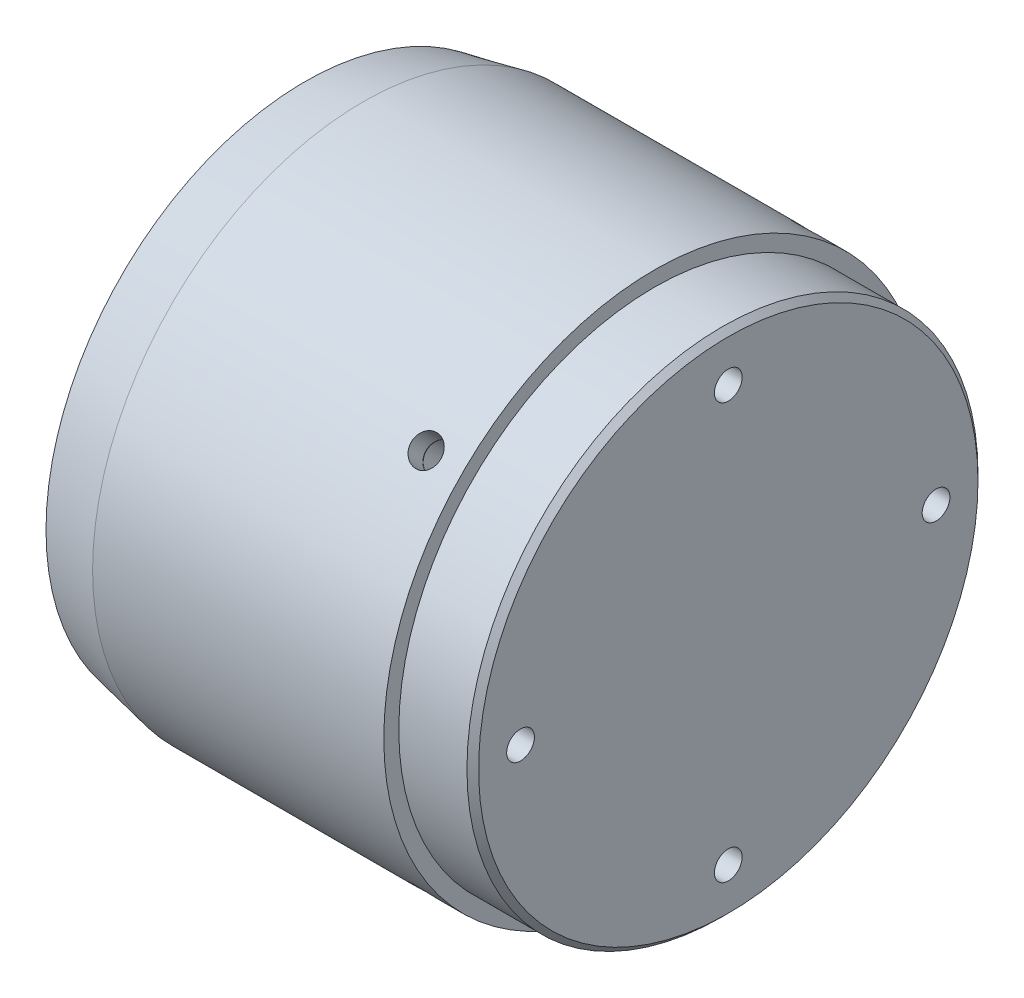
SolidWorks part; units mm, degrees
material "6061 Alloy"
ref_plane "Front Plane" through (0, 0, 0) normal (0, 0, 1) x (1, 0, 0)
ref_plane "Top Plane" through (0, 0, 0) normal (0, 1, 0) x (1, 0, 0)
ref_plane "Right Plane" through (0, 0, 0) normal (1, 0, 0) x (0, 0, -1)
sketch "Sketch1" plane through (0, 0, 0) normal (0, 0, 1) x (1, 0, 0)
  line L0 (0, 0) -> (74.8253, 0) construction
  line L1 (10, 46.45) -> (60, 46.45)
  line L6 (0, 44.45) -> (10, 46.45)
  line L7 (0, 0) -> (0, 44.45) construction
  line L17 (60, 44.45) -> (60, 46.45)
  line L18 (60, 44.45) -> (60, 42.85)
  line L19 (60, 42.85) -> (40, 42.85)
  line L20 (40, 42.85) -> (40, 44.45)
  line L21 (40, 44.45) -> (0, 44.45)
  line L22 (40, 44.45) -> (60, 44.45) construction
  dimension "D1" = 88.9
  dimension "D2" = 60
  dimension "D3" = 10
  dimension "D4" = 20
  dimension "D5" = 2
  dimension "D6" = 1.6
revolve "Revolve1" add sketch "Sketch1" angle 360 about L0
sketch "Sketch2" plane through (0, 0, 0) normal (0, 0, 1) x (1, 0, 0)
  line L0 (0, 0) -> (60, 0) construction
  line L2 (60, -46.45) -> (60, 46.45) construction
  line L3 (60, 42.77) -> (47.3, 42.77)
  line L4 (60, 42.77) -> (60, 28.575)
  line L5 (60, 28.575) -> (47.3, 28.575)
  line L6 (47.3, 42.77) -> (47.3, 28.575)
  line L7 (60, -46.45) -> (60, 46.45) construction
  line L8 (60, 42.85) -> (0, 42.85) construction
  line L9 (0, 44.45) -> (0, -44.45) construction
  dimension "D1" = 12.7
  dimension "D2" = 28.575
  dimension "D3" = 0.08
revolve "Revolve2" add sketch "Sketch2" angle 360 about L0
sketch "Sketch3" plane through (60, 0, 0) normal (1, 0, 0) x (0, 0, -1)
  line L0 (-35.6725, 0) -> (0, 0) construction
  line L1 (0, 35.6725) -> (0, 0) construction
  line L2 (35.6725, 0) -> (0, 0) construction
  line L3 (0, -35.6725) -> (0, 0) construction
  line L4 (-28.575, 0) -> (-42.77, 0) construction
  circle A0 centre (-35.6725, 0) radius 2.3812
  circle A1 centre (0, 35.6725) radius 2.3812
  circle A2 centre (35.6725, 0) radius 2.3812
  circle A3 centre (0, -35.6725) radius 2.3812
  circle A4 centre (0, 0) radius 28.575 construction
  circle A5 centre (0, 0) radius 42.77 construction
  point P13 (0, 0)
  dimension "D1" = 4.7625
  dimension "D3" = 4
extrude "Cut-Extrude1" cut sketch "Sketch3" against normal through all
ref_plane "Plane1" through (0, 32.8451, 32.8451) normal (0, 0.7071, 0.7071) x (-1, 0, 0)
sketch "Sketch4" plane through (0, 32.8451, 32.8451) normal (0, 0.7071, 0.7071) x (-1, 0, 0)
  line L0 (-53.65, 0) -> (0, 0) construction
  line L1 (-60, 46.45) -> (-60, -46.45) construction
  circle A0 centre (-53.65, 0) radius 2.54
  dimension "D1" = 5.08
  dimension "D2" = 6.35
extrude "Cut-Extrude2" cut sketch "Sketch4" against normal up to surface (17.9881 mm away) up to face at (60, 0, 28.575)
ref_axis "Axis1" through (60, 0, 0) along (-1, 0, 0)
pattern_circular "CirPattern1" count 4 over 360 about axis through (60, 0, 0) along (-1, 0, 0) of "Cut-Extrude2"
sketch "Sketch5" plane through (60, 0, 0) normal (1, 0, 0) x (0, 0, -1)
  line L0 (0, 0) -> (-20.2056, 20.2056) construction
  line L3 (0, 0) -> (0, 35.6725) construction
  line L5 (-21.9733, 11.3667) -> (-18.4378, 29.0444) construction
  line L6 (-29.0444, 18.4378) -> (-11.3667, 21.9733) construction
  line L7 (-29.0444, 18.4378) -> (-18.4378, 29.0444)
  line L8 (-18.4378, 29.0444) -> (-11.3667, 21.9733)
  line L9 (-11.3667, 21.9733) -> (-21.9733, 11.3667)
  line L10 (-21.9733, 11.3667) -> (-29.0444, 18.4378)
  circle A0 centre (0, 0) radius 28.575 construction
  point P10 (-20.2056, 20.2056)
  point P12 (-20.2056, 20.2056)
  dimension "D1" = 45
  dimension "D2" = 15
  dimension "D3" = 10
extrude "Cut-Extrude3" cut sketch "Sketch5" against normal up to surface (12.7 mm away) up to face at (47.3, 0, 33.2912)
fillet "Fillet1" radius 3.2 4 edges at (53.65, 14.1939, 24.8005) (53.65, 24.8005, 14.1939) (53.65, 18.4378, 29.0444) (53.65, 29.0444, 18.4378)
fillet "Fillet2" radius 3.2 1 edges at (40, 0, 44.45)
sketch "Sketch6" plane through (60, 0, 0) normal (1, 0, 0) x (0, 0, -1)
  circle A0 centre (0, 0) radius 43.875
  circle A1 centre (-35.6725, 0) radius 2.3813 construction
  circle A2 centre (0, -35.6725) radius 2.3812 construction
  circle A3 centre (35.6725, 0) radius 2.3813 construction
  circle A4 centre (0, 35.6725) radius 2.3812 construction
  circle A5 centre (-35.6725, 0) radius 2.3812
  circle A6 centre (0, -35.6725) radius 2.3812
  circle A7 centre (35.6725, 0) radius 2.3812
  circle A8 centre (0, 35.6725) radius 2.3812
  dimension "D1" = 87.75
extrude "Boss-Extrude1" add sketch "Sketch6" along normal blind 12.7 separate body
chamfer "Chamfer1" distance 1 angle 45 1 edges at (72.7, 0, -43.875)
